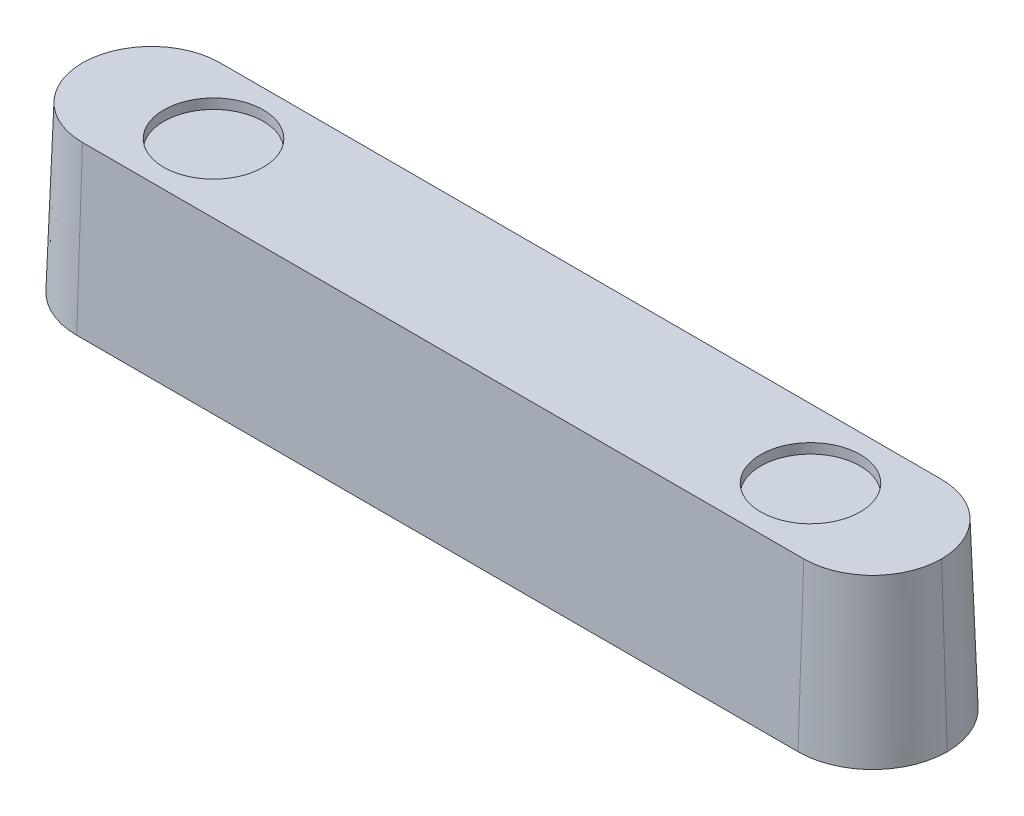
SolidWorks part; units mm, degrees
material "Stainless Steel (ferritic)"
ref_plane "Front Plane" through (0, 0, 0) normal (0, 0, 1) x (1, 0, 0)
ref_plane "Top Plane" through (0, 0, 0) normal (0, 1, 0) x (1, 0, 0)
ref_plane "Right Plane" through (0, 0, 0) normal (1, 0, 0) x (0, 0, -1)
sketch "Sketch1" plane through (0, 0, 0) normal (0, 1, 0) x (1, 0, 0)
  line L1 (-87.5, -15) -> (87.5, -15)
  line L2 (-87.5, -15) -> (-87.5, 15)
  line L3 (-87.5, 15) -> (87.5, 15)
  line L4 (87.5, -15) -> (87.5, 15)
  line L5 (-87.5, -15) -> (87.5, 15) construction
  line L6 (-87.5, 15) -> (87.5, -15) construction
  point P0 (0, 0)
  dimension "D1" = 30
  dimension "D2" = 175
extrude "Boss-Extrude1" add sketch "Sketch1" along normal blind 33
sketch "Sketch3" plane through (0, 33, 0) normal (0, 1, 0) x (1, 0, 0)
  line L0 (-60, 0) -> (60, 0) construction
  circle A0 centre (-60, 0) radius 10
  circle A1 centre (60, 0) radius 10
  dimension "D2" = 20
  dimension "D3" = 20
  dimension "D1" = 120
extrude "Cut-Extrude1" cut sketch "Sketch3" against normal blind 2
fillet "Fillet1" radius 15 4 edges at (-87.5, 16.5, -15) (87.5, 16.5, 15) (87.5, 16.5, -15) (-87.5, 16.5, 15)
sketch "Sketch4" plane through (0, 0, -15) normal (0, 0, -1) x (-1, 0, 0)
  line L0 (0, 17.1) -> (0, 0) construction
  circle A0 centre (0, 17.1) radius 4
  dimension "D1" = 8
  dimension "D2" = 17.1
extrude "Cut-Extrude2" cut sketch "Sketch4" against normal blind 4
draft "Draft3" type of draft neutral plane draft angle 2 faces to draft 6 face at (0, 16.5, 15) face at (81.5533, 16.5, 9.0533) face at (81.5533, 16.5, -9.0533) face at (-4, 17.1, -15) face at (-81.5533, 16.5, 9.0533) face at (-81.5533, 16.5, -9.0533) neutral plane through (0, 0, 0) neutral plane normal (0, -1, 0) reverse direction yes parameters "D1"=2
sketch3d "URDF Reference"
  line L0 (0, 0, 0) -> (10, 0, 0) construction
  line L1 (0, 0, 0) -> (0, 0, -10) construction
  point P0 (0, 0, 0)
  point P1 (0, 0, 0)
